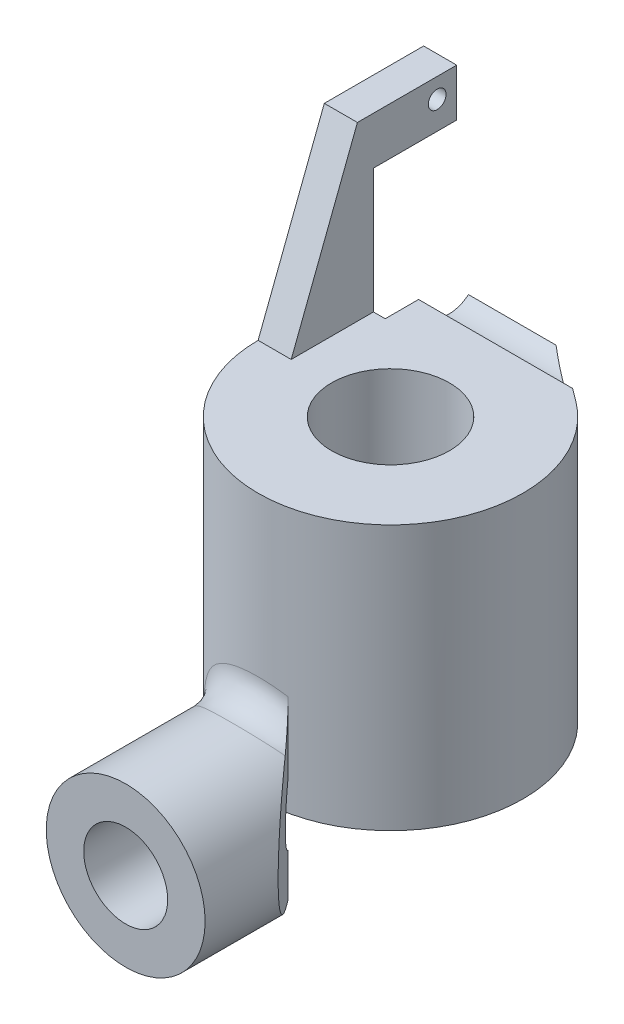
SolidWorks part; units mm, degrees
material "PE Low/Medium Density"
ref_plane "Front Plane" through (0, 0, 0) normal (0, 0, 1) x (1, 0, 0)
ref_plane "Top Plane" through (0, 0, 0) normal (0, 1, 0) x (1, 0, 0)
ref_plane "Right Plane" through (0, 0, 0) normal (1, 0, 0) x (0, 0, -1)
sketch "Sketch6" plane through (0, 0, 0) normal (0, 1, 0) x (1, 0, 0)
  line L0 (-12.7, 15.875) -> (0, 15.875)
  line L1 (-12.7, 15.875) -> (-12.7, 0)
  line L2 (0, 15.875) -> (7.62, 10.16)
  circle A0 centre (0, 0) radius 5.65
  arc A1 (-12.7, 0) -> (7.62, 10.16) centre (0, 0) ccw
  point P3 (0, 15.875)
  dimension "D1" = 11.3
  dimension "D2" = 25.4
  dimension "D3" = 15.875
  dimension "D4" = 12.7
extrude "MainBody" add sketch "Sketch6" along normal blind 25.4
sketch "Sketch8" plane through (0, 0, 0) normal (0, 0, 1) x (1, 0, 0)
  circle A0 centre (0, 0) radius 7.62
  circle A1 centre (0, 0) radius 4.0259
  dimension "D1" = 15.24
  dimension "D2" = 8.0518
extrude "ShaftAttachment" add sketch "Sketch8" against normal up to surface (15.24 mm away) from offset 25.4 up to face at (1.5698, 12.7, 3.1396)
fillet "Fillet1" radius 2.54 1 edges at (-0.2736, 7.6151, 12.6971)
sketch "Sketch9" plane through (0, 25.4, 0) normal (0, 1, 0) x (1, 0, 0)
  line L1 (0, 2.54) -> (0, -19.9115) construction
  line L3 (7.62, -25.4) -> (7.62, -11.3592) construction
  line L5 (14.0065, -14.1523) -> (8.9336, -9.0266)
  line L7 (0, 2.54) -> (14.0065, -14.1523) construction
  line L8 (2.6127, -12.4283) -> (7.62, -18.3958)
  line L9 (-5.8373, -2.358) -> (8.1692, -19.0503) construction
  circle A2 centre (0, 0) radius 12.7 construction
  arc A4 (14.0065, -14.1523) -> (7.62, -18.3958) centre (0, 0) cw
  arc A5 (2.6127, -12.4283) -> (8.9336, -9.0266) centre (0, 0) ccw
  dimension "D4" = 2.54
  dimension "D5" = 40
  dimension "D6" = 7.62
extrude "Cutout" cut sketch "Sketch9" against normal through all both and the other way through all contours L5 A5 L8 A4
ref_plane "Plane1" through (0, 0, -14.45) normal (0, 0, 1) x (1, 0, 0)
sketch "Sketch16" plane through (-12.7, 0, 0) normal (-1, 0, 0) x (0, 0, 1)
  line L0 (0, 25.4) -> (-6.35, 41.91)
  line L1 (-6.35, 41.91) -> (-15.875, 41.91)
  line L2 (-15.875, 41.91) -> (-15.875, 25.4)
  line L4 (-15.875, 25.4) -> (0, 25.4)
  line L5 (-15.875, 25.4) -> (0, 25.4) construction
  line L6 (-15.875, 25.4) -> (-15.875, 0) construction
  dimension "D1" = 16.51
  dimension "D2" = 9.525
extrude "Boss-Extrude2" add sketch "Sketch16" against normal blind 3.175
sketch "Sketch15" plane through (-12.7, 0, 0) normal (-1, 0, 0) x (0, 0, 1)
  line L0 (-15.875, 25.4) -> (0, 25.4) construction
  circle A0 centre (-14, 12.2039) radius 0.85
  circle A1 centre (-14, 25.654) radius 2.921
  circle A2 centre (-14, 40.004) radius 0.85
  point P4 (0, 0)
  point P5 (-14.45, 35.6464)
  point P6 (-15.2813, 35.9433)
  dimension "D1" = 1.7
  dimension "D3" = 5.842
  dimension "D2" = 13.4501
  dimension "D4" = 14
  dimension "D5" = 0.254
  dimension "D6" = 27.8
extrude "Cut-Extrude3" cut sketch "Sketch15" against normal through all both and the other way through all
sketch "Sketch13" plane through (-12.7, 0, 0) normal (-1, 0, 0) x (0, 0, 1)
  line L1 (-20.1087, 37.3456) -> (-7.8913, 37.3456)
  line L2 (-20.1087, 37.3456) -> (-20.1087, 14.8455)
  line L3 (-20.1087, 14.8455) -> (-7.8913, 14.8455)
  line L4 (-7.8913, 37.3456) -> (-7.8913, 14.8455)
  point P5 (0, 0)
  point P6 (-14, 12.2039)
  point P7 (-14, 14.8455)
  point P9 (0, 0)
  point P12 (-9.8725, 28.7056)
  point P13 (0, 0)
  dimension "D1" = 12.2174
  dimension "D2" = 2.6416
  dimension "D3" = 22.5001
extrude "Cut-Extrude1" cut sketch "Sketch13" against normal blind 4.3
